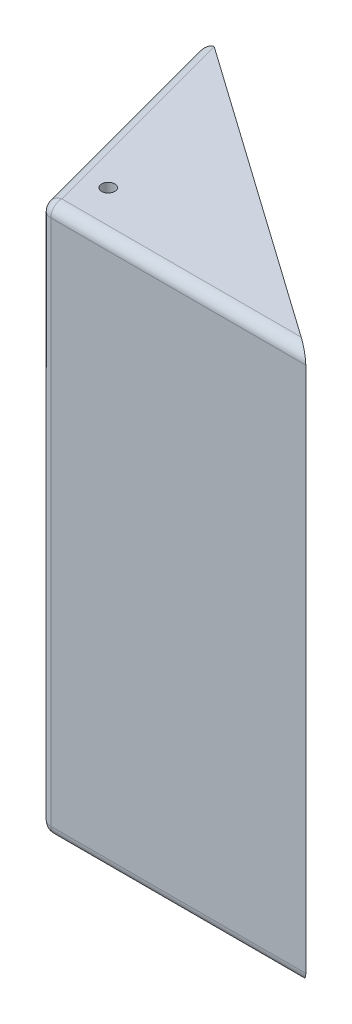
SolidWorks part; units mm, degrees
ref_plane "Front Plane" through (0, 0, 0) normal (0, 0, 1) x (1, 0, 0)
ref_plane "Top Plane" through (0, 0, 0) normal (0, 1, 0) x (1, 0, 0)
ref_plane "Right Plane" through (0, 0, 0) normal (1, 0, 0) x (0, 0, -1)
sketch "Sketch1" plane through (0, 0, 0) normal (0, 1, 0) x (1, 0, 0)
  line L0 (0, 0) -> (76.2, 0)
  line L5 (76.2, 0) -> (76.2, 63.5)
  line L6 (76.2, 63.5) -> (-17.0148, 63.5)
  line L7 (-17.0148, 63.5) -> (0, 0)
  dimension "D1" = 75
  dimension "D2" = 63.5
  dimension "D3" = 76.2
extrude "Boss-Extrude1" add sketch "Sketch1" along normal blind 3.175 contours L7 L0 L5 L6
sketch "Sketch2" plane through (0, 3.175, 0) normal (0, 1, 0) x (1, 0, 0)
  line L2 (76.2, 0) -> (0, 0)
  line L3 (0, 0) -> (-17.0148, 63.5)
  line L6 (76.2, 3.175) -> (2.4363, 3.175)
  line L7 (2.4363, 3.175) -> (-13.7278, 63.5)
  line L8 (76.2, 0) -> (76.2, 63.5) construction
  line L9 (76.2, 63.5) -> (-17.0148, 63.5) construction
  line L10 (76.2, 0) -> (76.2, 3.175)
  line L11 (-17.0148, 63.5) -> (-13.7278, 63.5)
  dimension "D1" = 3.175
  dimension "D4" = 3.175
extrude "Boss-Extrude3" add sketch "Sketch2" along normal blind 152.4
sketch "Sketch3" plane through (0, 155.575, 0) normal (0, 1, 0) x (1, 0, 0)
  line L0 (-17.0148, 63.5) -> (0, 0)
  line L1 (0, 0) -> (76.2, 0)
  line L2 (76.2, 0) -> (76.2, 63.5)
  line L3 (76.2, 63.5) -> (-17.0148, 63.5)
extrude "Boss-Extrude4" add sketch "Sketch3" along normal blind 3.175
fillet "Fillet1" radius 3.175 6 edges at (-17.0148, 79.375, -63.5) (38.1, 0, 0) (-8.5074, 0, -31.75) (0, 79.375, 0) (38.1, 158.75, 0) (-8.5074, 158.75, -31.75)
chamfer "Chamfer1" distance 3.175 angle 75 1 edges at (76.2, 79.375, -3.175) first distance on face at (76.2, 79.375, -26.5385)
sketch "Sketch4" plane through (0, 0, 0) normal (0, -1, 0) x (1, 0, 0)
  line L0 (2.4363, 0) -> (76.2, 0) construction
  line L1 (76.2, -3.175) -> (76.2, -63.5) construction
  circle A0 centre (6.35, -12.7) radius 1.905
  dimension "D1" = 3.81
  dimension "D2" = 12.7
  dimension "D3" = 69.85
extrude "Cut-Extrude1" cut sketch "Sketch4" against normal blind 158.75
sketch "Sketch6" plane through (0, 158.75, 0) normal (0, 1, 0) x (1, 0, 0)
  line L0 (-13.6988, 63.3918) -> (76.2, 0)
  line L1 (76.2, 0) -> (76.2, 63.5)
  line L5 (-13.6988, 63.3918) -> (-15.8826, 64.0757)
  line L6 (-15.8826, 64.0757) -> (76.2, 63.5)
extrude "Cut-Extrude2" cut sketch "Sketch6" against normal blind 254
